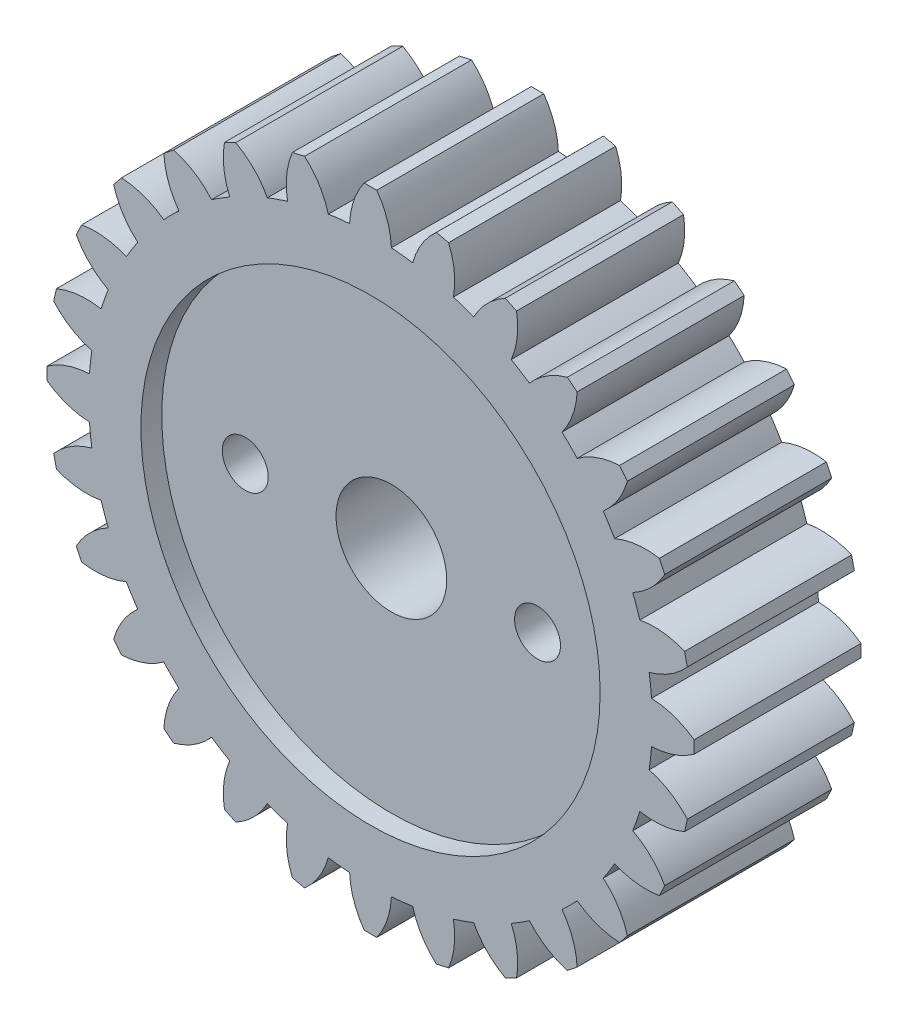
SolidWorks part; units mm, degrees
ref_plane "Front Plane" through (0, 0, 0) normal (0, 0, 1) x (1, 0, 0)
ref_plane "Top Plane" through (0, 0, 0) normal (0, 1, 0) x (1, 0, 0)
ref_plane "Right Plane" through (0, 0, 0) normal (1, 0, 0) x (0, 0, -1)
sketch "Sketch2" plane through (0, 0, 0) normal (0, 0, 1) x (1, 0, 0)
  line L0 (0, 0) -> (0, 18.136) construction
  line L1 (0.3, 15.5) -> (-0.3, 15.5)
  circle A0 centre (0, 0) radius 13.5
  circle A1 centre (0, 0) radius 2.65
  circle A2 centre (0, 0) radius 15.5 construction
  arc A3 (-0.3, 15.5) -> (-1, 13.4629) centre (2.7379, 13.3173) ccw
  arc A4 (0.3, 15.5) -> (1, 13.4629) centre (-2.7379, 13.3173) cw
  point P13 (0, 15.5)
  dimension "D1" = 27
  dimension "D2" = 5.3
  dimension "D6" = 3.7407
  dimension "D4" = 0.6
  dimension "D5" = 1
  dimension "D3" = 2
extrude "Boss-Extrude1" add sketch "Sketch2" along normal blind 8 contours A0 A1 region at (9.6134, 8.9258, 0)
extrude "Boss-Extrude2" add sketch "Sketch2<3>" along normal blind 8 contours A4 L1 A3 A0 region at (0, 14.3423, 0)
sketch "Sketch2<3>" plane through (0, 0, 0) normal (0, 0, 1) x (1, 0, 0) same geometry as "Sketch2"
pattern_circular "CirPattern1" count 28 over 360 about axis through (0, 0, 8) along (0, 0, 1) of "Boss-Extrude2"
sketch "Sketch3" plane through (0, 0, 8) normal (0, 0, 1) x (1, 0, 0)
  circle A0 centre (0, 0) radius 11
  dimension "D1" = 22
extrude "Cut-Extrude1" cut sketch "Sketch3" against normal blind 1
sketch "Sketch4" plane through (0, 0, 7) normal (0, 0, 1) x (1, 0, 0)
  line L0 (7, 0) -> (-7, 0)
  circle A0 centre (-7, 0) radius 1.1
  circle A1 centre (7, 0) radius 1.1
  point P5 (0, 0)
  dimension "D1" = 2.2
  dimension "D2" = 14
extrude "Cut-Extrude2" cut sketch "Sketch4" against normal through all contours A0 | A1 region at (-8.0689, 0, 7)
